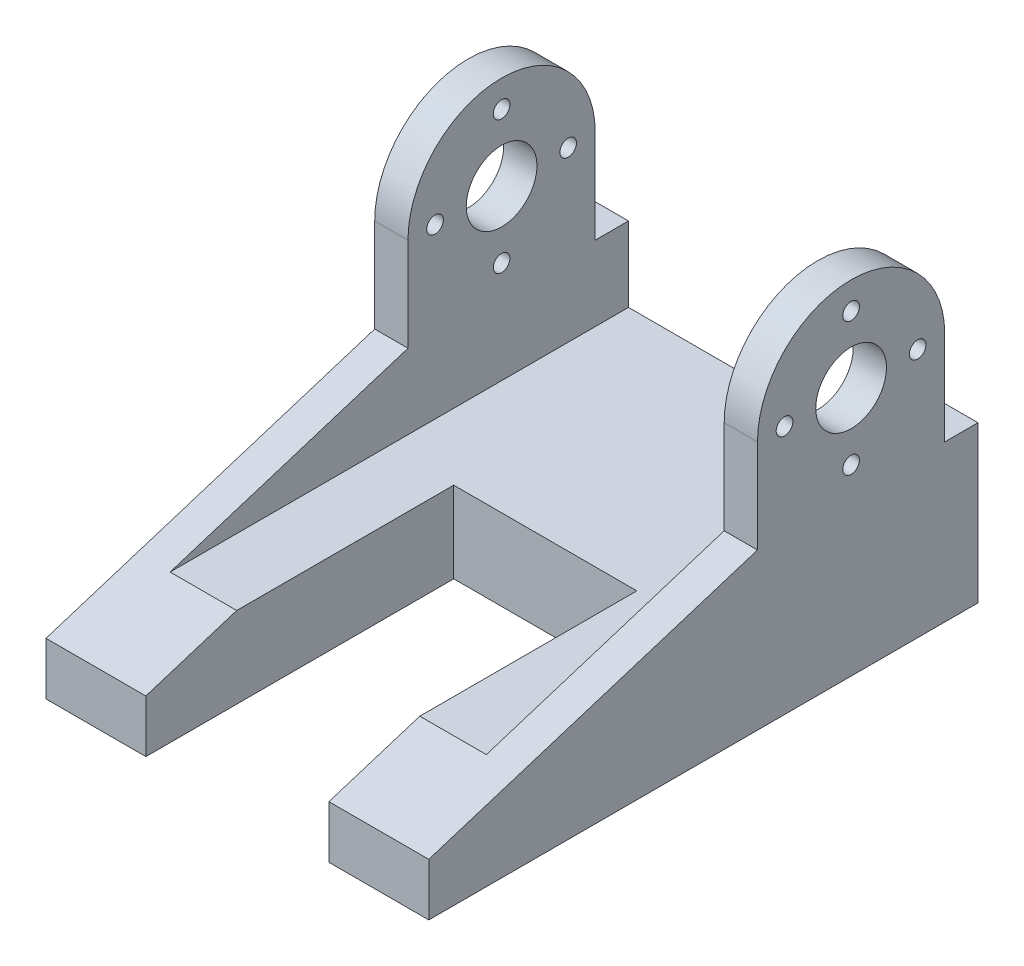
SolidWorks part; units mm, degrees
ref_plane "Front Plane" through (0, 0, 0) normal (0, 0, 1) x (1, 0, 0)
ref_plane "Top Plane" through (0, 0, 0) normal (0, 1, 0) x (1, 0, 0)
ref_plane "Right Plane" through (0, 0, 0) normal (1, 0, 0) x (0, 0, -1)
sketch "Sketch1" plane through (0, 0, 0) normal (0, 0, 1) x (1, 0, 0)
  line L1 (-25, 0) -> (25, 0)
  line L2 (-25, 0) -> (-25, -170)
  line L3 (-25, -170) -> (25, -170)
  line L4 (25, 0) -> (25, -170)
  dimension "D1" = 170
  dimension "D2" = 50
extrude "Boss-Extrude1" add sketch "Sketch1" against normal blind 55
sketch "Sketch2" plane through (0, 0, 0) normal (0, 0, 1) x (1, 0, 0)
  line L0 (25, 0) -> (-25, 0) construction
  line L1 (-17, 0) -> (17, 0)
  line L2 (-17, 0) -> (-17, -27)
  line L3 (-17, -27) -> (17, -27)
  line L4 (17, 0) -> (17, -27)
  line L5 (-25, 0) -> (-25, -170) construction
  dimension "D1" = 8
  dimension "D2" = 34
  dimension "D3" = 27
extrude "Cut-Extrude1" cut sketch "Sketch2" against normal through all
sketch "Sketch3" plane through (25, 0, 0) normal (1, 0, 0) x (0, 0, -1)
  line L0 (0, -170) -> (0, 0) construction
  line L1 (55, -27) -> (0, -27)
  line L2 (55, -27) -> (55, -24)
  line L3 (55, -24) -> (0, -24)
  line L4 (0, -27) -> (0, -24)
  line L5 (55, -170) -> (55, 0) construction
  line L7 (0, 0) -> (10, 0)
  line L8 (0, 0) -> (0, -24)
  line L9 (0, -24) -> (10, -24)
  line L10 (10, 0) -> (10, -24)
  line L11 (55, 0) -> (45, 0)
  line L12 (55, 0) -> (55, -24)
  line L13 (55, -24) -> (45, -24)
  line L14 (45, 0) -> (45, -24)
  circle A0 centre (27.5, -12.75) radius 10.25
  circle A1 centre (27.5, -12.75) radius 4.25
  circle A2 centre (27.5, -12.75) radius 8
  circle A3 centre (27.5, -4.75) radius 1
  circle A4 centre (35.5, -12.75) radius 1
  circle A5 centre (27.5, -20.75) radius 1
  circle A6 centre (19.5, -12.75) radius 1
  point P32 (27.5, -12.75)
  line M7 (0, 0) -> (0, -170)
  line M9 (55, -170) -> (55, 0)
  line M10 (55, 0) -> (0, 0)
  dimension "D2" = 11.25
  dimension "D3" = 27.5
  dimension "D4" = 20.5
  dimension "D7" = 8.5
  dimension "D8" = 16
  dimension "D9" = 4
  dimension "D1" = 3
  dimension "D5" = 10
  dimension "D6" = 10
extrude "Cut-Extrude2" cut sketch "Sketch3" against normal through all contours L14 L3 M10 M9 | L10 L3 M10 M7 | A2 A6 | A2 A6 | A1 | A2 A5 | A2 A5 | A2 A4 | A2 A4 | A2 A3 | A2 A3 region at (25, -12, -50) region at (25, -12, -5) region at (25, -12.75, -27.5) region at (25, -12.75, -35.0645) region at (25, -12.75, -35.913) region at (25, -5.1855, -27.5) region at (25, -4.337, -27.5) region at (25, -21.163, -27.5) region at (25, -20.3145, -27.5) region at (25, -12.75, -19.9355) region at (25, -12.75, -19.087)
sketch "Sketch4" plane through (0, 0, -10) normal (0, 0, 1) x (1, 0, 0)
  line L0 (-25, -24) -> (-17, -24) construction
  line L1 (-17, 0) -> (-19, 0)
  line L2 (-17, 0) -> (-17, -24)
  line L3 (-17, -24) -> (-19, -24)
  line L4 (-19, 0) -> (-19, -24)
  line L5 (0, 0) -> (0, -13.53) construction
  line L6 (19, 0) -> (19, -24)
  line L7 (17, -24) -> (19, -24)
  line L8 (17, 0) -> (17, -24)
  line L9 (17, 0) -> (19, 0)
  dimension "D1" = 2
extrude "Cut-Extrude3" cut sketch "Sketch4" against normal through all
sketch "Sketch5" plane through (25, 0, 0) normal (1, 0, 0) x (0, 0, -1)
  line L1 (10, 0) -> (45, 0)
  line L2 (10, 0) -> (10, -24)
  line L3 (10, -24) -> (45, -24)
  line L4 (45, 0) -> (45, -24)
  line L5 (38.75, -12.75) -> (38.75, -24)
  line L6 (16.25, -12.75) -> (10, -12.75)
  line L7 (16.25, -12.75) -> (16.25, -24)
  line L8 (16.25, -24) -> (10, -24)
  line L9 (10, -12.75) -> (10, -24)
  line L10 (38.75, -12.75) -> (45, -12.75)
  line L11 (38.75, -12.75) -> (38.75, -24)
  line L12 (38.75, -24) -> (45, -24)
  line L13 (45, -12.75) -> (45, -24)
  circle A0 centre (27.5, -12.75) radius 11.25
  line M8 (45, -24) -> (45, 0)
  line M9 (45, 0) -> (10, 0)
  line M10 (10, 0) -> (10, -24)
  dimension "D1" = 22.5
extrude "Cut-Extrude4" cut sketch "Sketch5" against normal through all contours A0 L10 L4 L6 M9 M10 | L7 L6 L2 L3 | L10 L5 L3 M8 region at (25, -0.3725, -27.5) region at (25, -18.375, -13.125) region at (25, -18.375, -41.875)
sketch "Sketch6" plane through (0, 0, 0) normal (0, 0, 1) x (1, 0, 0)
  line L1 (-19, -24) -> (19, -24)
  line L2 (-19, -24) -> (-19, -34)
  line L3 (-19, -34) -> (19, -34)
  line L4 (19, -24) -> (19, -34)
  dimension "D1" = 10
extrude "Cut-Extrude5" cut sketch "Sketch6" against normal through all
sketch "Sketch8" plane through (25, 0, 0) normal (1, 0, 0) x (0, 0, -1)
  line L0 (55, -170) -> (55, -24) construction
  line L1 (0, -170) -> (0, -24) construction
  line L2 (41.75, -132.5) -> (13.25, -132.5)
  line L3 (27.5, -132.5) -> (27.5, -179)
  line L4 (41.75, -179) -> (13.25, -179)
  line L5 (13.25, -132.5) -> (13.25, -179)
  line L7 (41.75, -132.5) -> (41.75, -179)
  line L11 (27.5, -167.75) -> (55, -167.75)
  line L12 (27.5, -167.75) -> (27.5, -170)
  line L13 (27.5, -170) -> (55, -170)
  line L14 (55, -167.75) -> (55, -170)
  line L16 (27.5, -167.75) -> (0, -167.75)
  line L17 (27.5, -167.75) -> (27.5, -170)
  line L18 (27.5, -170) -> (0, -170)
  line L19 (0, -167.75) -> (0, -170)
  circle A0 centre (27.5, -167.75) radius 10.25
  circle A1 centre (27.5, -12.75) radius 10.25
  line M4 (0, -24) -> (0, -170)
  line M5 (0, -170) -> (55, -170)
  line M6 (55, -170) -> (55, -24)
  dimension "D1" = 27.5
  dimension "D2" = 20.5
  dimension "D3" = 155
  dimension "D4" = 14.25
  dimension "D5" = 11.25
  dimension "D6" = 46.5
  dimension "D7" = 13.25
extrude "Cut-Extrude7" cut sketch "Sketch8" against normal through all contours A0 L3 L2 L5 L16 | A0 L11 L7 L2 L3 | L11 L7 M5 M6 | L5 L16 M4 M5 | A0 L16 L5 M5 | A0 L13 L7 L11 | L3 A0 L16 | L11 A0 L3 | L16 A0 L18 L3 | A0 L11 L3 M5 region at (25, -147.5157, -35.1704) region at (25, -147.5157, -19.8296) region at (25, -168.875, -48.375) region at (25, -168.8865, -39.7079) region at (25, -163.3998, -31.8502) region at (25, -163.3998, -23.1498) region at (25, -168.8704, -32.5838) region at (25, -168.8865, -15.2921) region at (25, -168.875, -6.625) region at (25, -168.8704, -22.4162)
sketch "Sketch9" plane through (0, 0, 0) normal (0, 0, 1) x (1, 0, 0)
  line L0 (-25, -167.75) -> (25, -167.75) construction
  line L1 (17, -167.75) -> (-17, -167.75)
  line L2 (17, -167.75) -> (17, -132.5)
  line L3 (17, -132.5) -> (-17, -132.5)
  line L4 (-17, -167.75) -> (-17, -132.5)
  line L5 (-25, -132.5) -> (25, -132.5) construction
  line L7 (-25, -24) -> (-25, -167.75) construction
  line L9 (25, -167.75) -> (25, -24) construction
  dimension "D1" = 8
  dimension "D2" = 8
extrude "Cut-Extrude8" cut sketch "Sketch9" against normal through all
sketch "Sketch11" plane through (25, 0, 0) normal (1, 0, 0) x (0, 0, -1)
  line L0 (27.5, -157.5) -> (27.5, -147.5)
  line L2 (27.5, -147.5) -> (55, -147.5)
  line L3 (27.5, -147.5) -> (27.5, -167.75)
  line L4 (27.5, -167.75) -> (55, -167.75)
  line L5 (55, -147.5) -> (55, -167.75)
  line L6 (27.5, -147.5) -> (0, -147.5)
  line L7 (27.5, -147.5) -> (27.5, -167.75)
  line L8 (27.5, -167.75) -> (0, -167.75)
  line L9 (0, -147.5) -> (0, -167.75)
  circle A0 centre (27.5, -167.75) radius 10.25
  arc A1 (38.75, -12.75) -> (16.25, -12.75) centre (27.5, -12.75) ccw construction
  line M1 (0, -167.75) -> (13.25, -167.75)
  line M2 (13.25, -167.75) -> (13.25, -132.5)
  line M4 (41.75, -132.5) -> (41.75, -167.75)
  line M5 (41.75, -167.75) -> (55, -167.75)
  line M6 (55, -167.75) -> (55, -24)
  line M12 (0, -24) -> (0, -167.75)
  dimension "D1" = 155
  dimension "D2" = 20.5
  dimension "D3" = 10
extrude "Cut-Extrude9" cut sketch "Sketch11" against normal through all contours A0 L0 L6 L8 M2 | A0 L4 L2 L0 M4 | L2 M4 M5 M6 | L6 M2 M12 M1 region at (25, -155.3124, -19.2638) region at (25, -155.3124, -35.7362) region at (25, -157.625, -48.375) region at (25, -157.625, -6.625)
sketch "Sketch12" plane through (25, 0, 0) normal (1, 0, 0) x (0, 0, -1)
  line L1 (13.25, -132.5) -> (41.75, -132.5)
  line L2 (13.25, -132.5) -> (13.25, -147.5)
  line L3 (13.25, -147.5) -> (41.75, -147.5)
  line L4 (41.75, -132.5) -> (41.75, -147.5)
extrude "Boss-Extrude2" add sketch "Sketch12" against normal blind 8
ref_plane "Plane1" through (0, 0, 0) normal (1, 0, 0) x (0, 0, -1)
mirror "Mirror1" about plane through (0, 0, 0) normal (1, 0, 0) of "Boss-Extrude2"
sketch "Sketch14" plane through (0, 0, 0) normal (0, 0, 1) x (1, 0, 0)
  line L0 (17, -148.55) -> (17, -158.75) construction
  line L1 (-17, -132.5) -> (17, -132.5)
  line L2 (-17, -132.5) -> (-17, -147.5)
  line L3 (-17, -147.5) -> (17, -147.5)
  line L4 (17, -132.5) -> (17, -147.5)
  line L5 (-17, -147.5) -> (17, -147.5)
  line L6 (-17, -147.5) -> (-17, -157.75)
  line L7 (-17, -157.75) -> (17, -157.75)
  line L8 (17, -147.5) -> (17, -157.75)
  line M11 (-17, -147.5) -> (-17, -132.5)
  line M12 (-17, -132.5) -> (17, -132.5)
  line M13 (17, -132.5) -> (17, -147.5)
  dimension "D1" = 10.25
extrude "Boss-Extrude3" add sketch "Sketch14" against normal blind 13.25 contours L3 M11 M13 M12 | L8 L3 L6 L7 region at (0, -140, 0) region at (0, -152.625, 0)
ref_plane "Plane2" through (0, 0, -27.5) normal (0, 0, 1) x (1, 0, 0)
mirror "Mirror2" about plane through (0, 0, -27.5) normal (0, 0, 1) of "Boss-Extrude3"
sketch "Sketch16" plane through (25, 0, 0) normal (1, 0, 0) x (0, 0, -1)
  line L0 (41.75, -132.5) -> (13.25, -132.5) construction
  line L1 (13.25, -132.5) -> (13.25, -147.5) construction
  circle A1 centre (16.5, -135.75) radius 2.5
  circle A2 centre (16.5, -135.75) radius 4.5
  circle A3 centre (38.5, -135.75) radius 4.5
  dimension "D1" = 3.25
  dimension "D2" = 3.25
  dimension "D3" = 2
extrude "Cut-Extrude13" cut sketch "Sketch16" against normal blind 8 contours A1 | A2 A1 | A3 region at (25, -135.75, -16.5) region at (25, -135.75, -12.1273) region at (25, -135.75, -38.5)
mirror "Mirror3" about plane through (0, 0, 0) normal (1, 0, 0) of "Cut-Extrude13"
sketch "Sketch17" plane through (25, 0, 0) normal (1, 0, 0) x (0, 0, -1)
  line L0 (55, -147.5) -> (55, -24) construction
  line L1 (27.5, -1.5) -> (55, -1.5)
  line L2 (27.5, -1.5) -> (27.5, -51.5)
  line L3 (27.5, -51.5) -> (55, -51.5)
  line L4 (55, -1.5) -> (55, -51.5)
  line L8 (55, -51.5) -> (0, -51.5)
  line L9 (55, -51.5) -> (55, -157.75)
  line L10 (55, -157.75) -> (0, -157.75)
  line L11 (0, -51.5) -> (0, -157.75)
  arc A0 (38.75, -12.75) -> (16.25, -12.75) centre (27.5, -12.75) ccw construction
  circle M2 centre (16.5, -135.75) radius 4.5
  circle M3 centre (38.5, -135.75) radius 4.5
  line M4 (0, -147.5) -> (55, -147.5)
  line M5 (55, -147.5) -> (55, -24)
  line M11 (0, -24) -> (0, -147.5)
  dimension "D1" = 50
extrude "Cut-Extrude15" cut sketch "Sketch17" against normal through all contours L3 L8 M11 M4 M5 M2 M3 | L11 L10 L9 M4 | M3 | M2 region at (25, -98.6049, -27.5) region at (25, -152.625, -27.5) region at (25, -135.75, -16.5) region at (25, -135.75, -38.5)
sketch "Sketch18" plane through (25, 0, 0) normal (1, 0, 0) x (0, 0, -1)
  line L1 (38.75, -24) -> (-71.25, -24)
  line L2 (38.75, -24) -> (38.75, -51.5)
  line L3 (38.75, -51.5) -> (-71.25, -51.5)
  line L4 (-71.25, -24) -> (-71.25, -51.5)
  line L6 (38.75, -24) -> (68.75, -24)
  line L7 (38.75, -24) -> (38.75, -51.5)
  line L8 (38.75, -51.5) -> (68.75, -51.5)
  line L9 (68.75, -24) -> (68.75, -51.5)
  line M8 (0, -24) -> (0, -51.5)
  line M9 (0, -51.5) -> (55, -51.5)
  line M10 (55, -51.5) -> (55, -24)
  line M11 (55, -24) -> (38.75, -24)
  line M15 (16.25, -24) -> (0, -24)
  dimension "D1" = 110
  dimension "D2" = 30
extrude "Boss-Extrude4" add sketch "Sketch18" against normal blind 50 contours L1 L4 L3 M8 | L9 L6 L8 M10 | L2 L1 M15 M8 M9 | L2 M11 M9 M10 region at (25, -37.75, -19.375) region at (25, -37.75, -46.875) region at (25, -37.75, -61.875) region at (25, -37.75, 35.625)
sketch "Sketch19" plane through (0, 0, 71.25) normal (0, 0, 1) x (1, 0, 0)
  line L1 (-19, -24) -> (19, -24)
  line L2 (-19, -24) -> (-19, -31)
  line L3 (-19, -31) -> (19, -31)
  line L4 (19, -24) -> (19, -31)
  dimension "D1" = 7
extrude "Cut-Extrude16" cut sketch "Sketch19" against normal through all
sketch "Sketch20" plane through (25, 0, 0) normal (1, 0, 0) x (0, 0, -1)
  line L1 (-71.25, -24) -> (68.75, -24)
  line L2 (-71.25, -24) -> (-71.25, -51.5)
  line L3 (-71.25, -51.5) -> (68.75, -51.5)
  line L4 (68.75, -24) -> (68.75, -51.5)
  line L5 (16.25, -24) -> (-13.75, -24)
  line L6 (16.25, -24) -> (16.25, -51.5)
  line L7 (16.25, -51.5) -> (-13.75, -51.5)
  line L8 (-13.75, -24) -> (-13.75, -51.5)
  line L10 (-13.75, -51.5) -> (-71.25, -51.5)
  line L11 (-13.75, -51.5) -> (-13.75, -24)
  line L12 (-13.75, -24) -> (-71.25, -24)
  line L13 (-71.25, -51.5) -> (-71.25, -24)
  line M8 (-71.25, -24) -> (-71.25, -51.5)
  line M9 (-71.25, -51.5) -> (68.75, -51.5)
  dimension "D1" = 30
extrude "Cut-Extrude17" cut sketch "Sketch20" against normal through all contours L8 L1 M8 M9 region at (25, -37.75, 42.5)
sketch "Sketch21" plane through (25, 0, 0) normal (1, 0, 0) x (0, 0, -1)
  line L0 (16.25, -24) -> (-13.75, -51.5)
  line L1 (16.25, -24) -> (-13.75, -24)
  line L2 (16.25, -24) -> (16.25, -51.5)
  line L3 (16.25, -51.5) -> (-13.75, -51.5)
  line L4 (-13.75, -24) -> (-13.75, -51.5)
  line M6 (16.25, -24) -> (-13.75, -24)
  line M7 (-13.75, -24) -> (-13.75, -51.5)
extrude "Cut-Extrude18" cut sketch "Sketch21" against normal through all contours L0 M6 M7 region at (25, -33.1667, 3.75)
sketch "Sketch22" plane through (25, 0, 0) normal (1, 0, 0) x (0, 0, -1)
  line L3 (68.75, -51.5) -> (-13.75, -51.5)
  line L4 (68.75, -51.5) -> (68.75, -54)
  line L5 (68.75, -54) -> (-13.75, -54)
  line L6 (-13.75, -51.5) -> (-13.75, -54)
  dimension "D1" = 2.5
extrude "Boss-Extrude5" add sketch "Sketch22" against normal blind 50
sketch "Sketch24" plane through (25, 0, 0) normal (1, 0, 0) x (0, 0, -1)
  line L1 (68.75, -24) -> (46.75, -24)
  line L2 (68.75, -24) -> (68.75, -41)
  line L3 (68.75, -41) -> (46.75, -41)
  line L4 (46.75, -24) -> (46.75, -41)
  dimension "D1" = 17
  dimension "D2" = 22
extrude "Cut-Extrude19" cut sketch "Sketch24" against normal through all
sketch "Sketch25" plane through (0, -31, 0) normal (0, 1, 0) x (1, 0, 0)
  line L1 (-19, 46.75) -> (19, 46.75)
  line L2 (-19, 46.75) -> (-19, 8.6136)
  line L3 (-19, 8.6136) -> (19, 8.6136)
  line L4 (19, 46.75) -> (19, 8.6136)
extrude "Cut-Extrude20" cut sketch "Sketch25" against normal blind 10
sketch "Sketch27" plane through (0, -41, 0) normal (0, 1, 0) x (1, 0, 0)
  line L0 (-25, 68.75) -> (25, 68.75) construction
  line L1 (19, 8.6136) -> (-19, 8.6136)
  line L2 (19, 8.6136) -> (19, 68.75)
  line L3 (19, 68.75) -> (-19, 68.75)
  line L4 (-19, 8.6136) -> (-19, 68.75)
extrude "Boss-Extrude6" add sketch "Sketch27" along normal blind 8.6
sketch "Sketch29" plane through (0, 0, -8.6136) normal (0, 0, -1) x (-1, 0, 0)
  line L1 (-19, -31) -> (19, -31)
  line L2 (-19, -31) -> (-19, -32.4)
  line L3 (-19, -32.4) -> (19, -32.4)
  line L4 (19, -31) -> (19, -32.4)
extrude "Cut-Extrude21" cut sketch "Sketch29" against normal through all
sketch "Sketch30" plane through (-25, 0, 0) normal (-1, 0, 0) x (0, 0, 1)
  line L0 (-68.75, -32.4) -> (-68.75, -41) construction
  line L1 (-38.75, -24) -> (31.25, -24)
  line L2 (-38.75, -24) -> (-38.75, -53.9144)
  line L3 (-38.75, -53.9144) -> (31.25, -53.9144)
  line L4 (31.25, -24) -> (31.25, -53.9144)
  line L5 (-16.25, -24) -> (31.25, -38.9572)
  line L6 (31.25, -38.9572) -> (31.25, -53.9144)
  line L7 (-16.25, -24) -> (-16.25, -32.4)
  line L8 (-46.75, -32.4) -> (-7.0864, -32.4) construction
  line L9 (-16.25, -32.4) -> (-7.0864, -32.4)
  line L10 (-7.0864, -32.4) -> (-16.25, -24)
  line M5 (13.75, -54) -> (13.75, -51.5)
  line M6 (13.75, -51.5) -> (-16.25, -24)
  dimension "D1" = 100
extrude "Boss-Extrude7" add sketch "Sketch30" against normal blind 50 contours L5 L3 L4 M6 M5 | L7 L9 L10 region at (-25, -40.9436, 13.5151)
sketch "Sketch31" plane through (0, 0, -68.75) normal (0, 0, -1) x (-1, 0, 0)
  line L1 (-19, -24) -> (19, -24)
  line L2 (-19, -24) -> (-19, -41)
  line L3 (-19, -41) -> (19, -41)
  line L4 (19, -24) -> (19, -41)
extrude "Cut-Extrude22" cut sketch "Sketch31" against normal through all
sketch "Sketch32" plane through (25, 0, 0) normal (1, 0, 0) x (0, 0, -1)
  line L0 (-31.25, -38.9572) -> (-31.25, -53.9144) construction
  line L1 (68.75, -54) -> (-31.25, -54)
  line L2 (68.75, -54) -> (68.75, -51)
  line L3 (68.75, -51) -> (-31.25, -51)
  line L4 (-31.25, -54) -> (-31.25, -51)
  dimension "D1" = 3
extrude "Cut-Extrude23" cut sketch "Sketch32" against normal through all
sketch "Sketch33" plane through (0, -41, 0) normal (0, 1, 0) x (1, 0, 0)
  line L0 (19, -31.25) -> (-19, -31.25) construction
  line L1 (11, -31.25) -> (-11, -31.25)
  line L2 (11, -31.25) -> (11, 13.75)
  line L3 (11, 13.75) -> (-11, 13.75)
  line L4 (-11, -31.25) -> (-11, 13.75)
  line L6 (-25, 68.75) -> (-10, 68.75)
  line L7 (-25, 68.75) -> (-25, 46.75)
  line L8 (-25, 46.75) -> (-10, 46.75)
  line L9 (-10, 68.75) -> (-10, 46.75)
  line L10 (25, 68.75) -> (10, 68.75)
  line L11 (25, 68.75) -> (25, 46.75)
  line L12 (25, 46.75) -> (10, 46.75)
  line L13 (10, 68.75) -> (10, 46.75)
  line L15 (19, 16.25) -> (19, -31.25) construction
  line L16 (-19, -31.25) -> (-19, 46.75) construction
  line L18 (-10, 68.75) -> (10, 68.75)
  line L19 (-10, 68.75) -> (-10, 58.75)
  line L20 (-10, 58.75) -> (10, 58.75)
  line L21 (10, 68.75) -> (10, 58.75)
  line M10 (-25, 46.75) -> (-19, 46.75)
  line M12 (-19, -31.25) -> (19, -31.25)
  line M14 (19, 46.75) -> (25, 46.75)
  line M15 (25, 46.75) -> (25, 68.75)
  line M16 (25, 68.75) -> (-25, 68.75)
  line M17 (-25, 68.75) -> (-25, 46.75)
  dimension "D1" = 8
  dimension "D2" = 8
  dimension "D3" = 45
  dimension "D4" = 15
  dimension "D5" = 15
  dimension "D6" = 10
extrude "Cut-Extrude24" cut sketch "Sketch33" against normal through all contours L9 L8 M16 M17 M10 | L13 L12 M16 M14 M15 | L9 L20 L13 M16 | L4 L2 L3 M12 region at (0, -41, 8.75) region at (-17.5, -41, -57.75) region at (0, -41, -63.75) region at (17.5, -41, -57.75)
sketch "Sketch34" plane through (0, -41, 0) normal (0, 1, 0) x (1, 0, 0)
  line L0 (-10, 58.75) -> (10, 58.75) construction
  line L1 (-4, 58.75) -> (4, 58.75)
  line L2 (-4, 58.75) -> (-4, 46.75)
  line L3 (-4, 46.75) -> (4, 46.75)
  line L4 (4, 58.75) -> (4, 46.75)
  line L5 (-10, 58.75) -> (-10, 46.75) construction
  line L6 (10, 58.75) -> (10, 46.75) construction
  dimension "D1" = 6
  dimension "D2" = 6
  dimension "D3" = 12
extrude "Cut-Extrude25" cut sketch "Sketch34" against normal through all
sketch "Sketch36" plane through (0, -41, 0) normal (0, 1, 0) x (1, 0, 0)
  line L1 (19, -31.25) -> (-19, -31.25)
  line L2 (19, -31.25) -> (19, 58.75)
  line L3 (19, 58.75) -> (-19, 58.75)
  line L4 (-19, -31.25) -> (-19, 58.75)
  line L5 (-4, 58.75) -> (4, 58.75)
  line L6 (-4, 58.75) -> (-4, 46.75)
  line L7 (-4, 46.75) -> (4, 46.75)
  line L8 (4, 58.75) -> (4, 46.75)
  line L9 (10, 58.75) -> (19, 58.75)
  line L10 (10, 58.75) -> (10, 46.75)
  line L11 (10, 46.75) -> (19, 46.75)
  line L12 (19, 58.75) -> (19, 46.75)
  line L13 (-10, 58.75) -> (-19, 58.75)
  line L14 (-10, 58.75) -> (-10, 46.75)
  line L15 (-10, 46.75) -> (-19, 46.75)
  line L16 (-19, 58.75) -> (-19, 46.75)
  line L17 (-11, 13.75) -> (11, 13.75)
  line L18 (-11, 13.75) -> (-11, -31.25)
  line L19 (-11, -31.25) -> (11, -31.25)
  line L20 (11, 13.75) -> (11, -31.25)
  line M1 (4, 46.75) -> (-4, 46.75)
  line M2 (-4, 46.75) -> (-4, 58.75)
  line M3 (-4, 58.75) -> (-10, 58.75)
  line M4 (-10, 58.75) -> (-10, 46.75)
  line M5 (-10, 46.75) -> (-19, 46.75)
  line M6 (-19, 46.75) -> (-19, -31.25)
  line M7 (-19, -31.25) -> (-11, -31.25)
  line M8 (-11, -31.25) -> (-11, 13.75)
  line M9 (-11, 13.75) -> (11, 13.75)
  line M10 (11, 13.75) -> (11, -31.25)
  line M11 (11, -31.25) -> (19, -31.25)
  line M12 (19, -31.25) -> (19, 46.75)
  line M13 (19, 46.75) -> (10, 46.75)
  line M14 (10, 46.75) -> (10, 58.75)
  line M15 (10, 58.75) -> (4, 58.75)
  line M16 (4, 58.75) -> (4, 46.75)
extrude "Boss-Extrude8" add sketch "Sketch36" along normal blind 8 contours M16 M1 M2 M3 M4 M5 M6 M7 M8 M9 M10 M11 M12 M13 M14 M15 region at (0, -41, -18.522)
sketch "Sketch37" plane through (25, 0, 0) normal (1, 0, 0) x (0, 0, -1)
  line L0 (-31.25, -38.9572) -> (-31.25, -51) construction
  line L1 (58.75, -51) -> (-31.25, -51)
  line L2 (58.75, -51) -> (58.75, -42)
  line L3 (58.75, -42) -> (-31.25, -42)
  line L4 (-31.25, -51) -> (-31.25, -42)
  line L5 (-31.25, -38.9572) -> (-12.3315, -33)
  line L6 (-12.3315, -33) -> (-31.25, -33)
  line L7 (-12.3315, -33) -> (-12.3315, -38.9572)
  line L8 (-12.3315, -38.9572) -> (-31.25, -38.9572)
  line L9 (-31.25, -33) -> (-31.25, -38.9572)
  line L11 (58.75, -42) -> (46.75, -42)
  line L12 (58.75, -42) -> (58.75, -51)
  line L13 (58.75, -51) -> (46.75, -51)
  line L14 (46.75, -42) -> (46.75, -51)
  line M7 (-31.25, -51) -> (46.75, -51)
  line M8 (46.75, -51) -> (46.75, -24)
  line M13 (16.25, -24) -> (-31.25, -38.9572)
  line M14 (-31.25, -38.9572) -> (-31.25, -51)
  dimension "D1" = 9
extrude "Cut-Extrude27" cut sketch "Sketch37" against normal through all contours L3 M8 M14 M7 | L6 L9 M13 | L2 L3 L1 M8 region at (25, -34.9857, 24.9438) region at (25, -46.5, -52.75) region at (25, -46.5, -7.75)
fillet "Fillet1" radius 10 2 edges at (-7, -42, -58.75) (7, -42, -58.75)
sketch "Sketch38" plane through (0, 0, 0) normal (0, 1, 0) x (1, 0, 0)
  line L6 (-11, -31.25) -> (-25, -31.25) construction
  line L7 (-25, 46.75) -> (-23, 46.75)
  line L8 (-25, 46.75) -> (-25, -31.25)
  line L9 (-25, -31.25) -> (-23, -31.25)
  line L10 (-23, 46.75) -> (-23, -31.25)
  line L11 (25, -31.25) -> (11, -31.25) construction
  line L12 (25, 46.75) -> (23, 46.75)
  line L13 (25, 46.75) -> (25, -31.25)
  line L14 (25, -31.25) -> (23, -31.25)
  line L15 (23, 46.75) -> (23, -31.25)
  line L17 (-23, -31.25) -> (23, -31.25)
  line L18 (-23, -31.25) -> (-23, -23.25)
  line L19 (-23, -23.25) -> (23, -23.25)
  line L20 (23, -31.25) -> (23, -23.25)
  dimension "D1" = 2
  dimension "D2" = 2
  dimension "D3" = 8
extrude "Cut-Extrude29" cut sketch "Sketch38" against normal through all both and the other way through all contours L10 L7 L8 L9 | L12 L15 L14 L13 | L19 L10 L17 L15 region at (-24, 0, -7.75) region at (0, 0, 27.25) region at (24, 0, -7.75)
sketch "Sketch39" plane through (23, 0, 0) normal (1, 0, 0) x (0, 0, -1)
  line L0 (46.75, -24) -> (38.75, -24) construction
  line L1 (42.75, -24) -> (64.9734, -24)
  line L2 (42.75, -24) -> (42.75, -43.4413)
  line L3 (42.75, -43.4413) -> (64.9734, -43.4413)
  line L4 (64.9734, -24) -> (64.9734, -43.4413)
extrude "Cut-Extrude30" cut sketch "Sketch39" against normal through all
sketch "Sketch41" plane through (0, -42, 0) normal (0, -1, 0) x (1, 0, 0)
  line L1 (-23, 23.25) -> (23, 23.25)
  line L2 (-23, 23.25) -> (-23, -42.75)
  line L3 (-23, -42.75) -> (23, -42.75)
  line L4 (23, 23.25) -> (23, -42.75)
  line L5 (-11, 23.25) -> (11, 23.25)
  line L6 (-11, 23.25) -> (-11, -13.75)
  line L7 (-11, -13.75) -> (11, -13.75)
  line L8 (11, 23.25) -> (11, -13.75)
  line M1 (-23, 23.25) -> (-23, -42.75)
  line M2 (-23, -42.75) -> (23, -42.75)
  line M3 (23, -42.75) -> (23, 23.25)
  line M4 (23, 23.25) -> (11, 23.25)
  line M5 (11, 23.25) -> (11, -13.75)
  line M6 (11, -13.75) -> (-11, -13.75)
  line M7 (-11, -13.75) -> (-11, 23.25)
  line M8 (-11, 23.25) -> (-23, 23.25)
extrude "Boss-Extrude9" add sketch "Sketch41" along normal blind 0.75 contours M8 M1 M2 M3 M4 M5 M6 M7 region at (0, -42, -15.0619)
